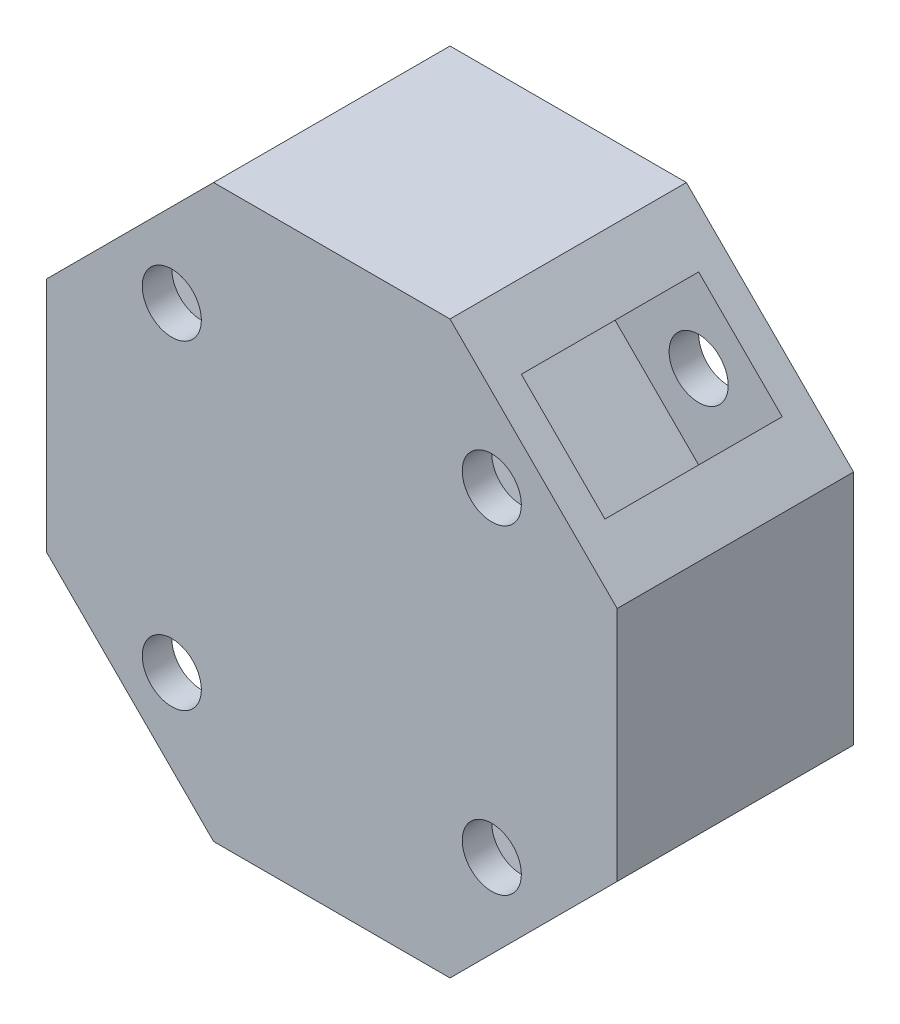
SolidWorks part; units mm, degrees
ref_plane "Front Plane" through (0, 0, 0) normal (0, 0, 1) x (1, 0, 0)
ref_plane "Top Plane" through (0, 0, 0) normal (0, 1, 0) x (1, 0, 0)
ref_plane "Right Plane" through (0, 0, 0) normal (1, 0, 0) x (0, 0, -1)
sketch "Sketch1" plane through (0, 0, 0) normal (0, 0, 1) x (1, 0, 0)
  line L0 (-30.6605, 12.7) -> (-30.6605, -12.7)
  line L1 (-12.7, -30.6605) -> (12.7, -30.6605)
  line L2 (12.7, -30.6605) -> (30.6605, -12.7)
  line L3 (30.6605, -12.7) -> (30.6605, 12.7)
  line L4 (30.6605, 12.7) -> (12.7, 30.6605)
  line L5 (12.7, 30.6605) -> (-12.7, 30.6605)
  line L6 (-12.7, 30.6605) -> (-30.6605, 12.7)
  line L7 (-30.6605, -12.7) -> (-12.7, -30.6605)
  line L8 (0, 0) -> (0, 37.9758) construction
  circle A0 centre (0, 0) radius 30.6605 construction
  dimension "D1" = 25.4
  dimension "D2" = 12.7
extrude "Boss-Extrude1" add sketch "Sketch1" along normal blind 25.4
sketch "Sketch2" plane through (21.6803, 21.6803, 0) normal (0.7071, 0.7071, 0) x (0, 0, -1)
  line L0 (-25.4, 0) -> (0, 0) construction
  line L1 (-25.4, -12.7) -> (-25.4, 12.7) construction
  line L2 (-12.7, 0) -> (-12.7, 12.7) construction
  line L3 (-25.4, 12.7) -> (0, 12.7) construction
  line L5 (-3.175, -6.35) -> (-22.225, -6.35)
  line L6 (-3.175, -6.35) -> (-3.175, 6.35)
  line L7 (-3.175, 6.35) -> (-22.225, 6.35)
  line L8 (-22.225, -6.35) -> (-22.225, 6.35)
  line L9 (-3.175, -6.35) -> (-22.225, 6.35) construction
  line L10 (-3.175, 6.35) -> (-22.225, -6.35) construction
  dimension "D1" = 19.05
  dimension "D2" = 12.7
extrude "Cut-Extrude1" cut sketch "Sketch2" against normal blind 12.7
ref_plane "Plane1" through (0, 0, 0) normal (1, 0, 0) x (0, 0, -1)
mirror "Mirror1" about plane through (0, 0, 0) normal (1, 0, 0) of "Cut-Extrude1"
ref_plane "Plane2" through (0, 0, 0) normal (0, 1, 0) x (1, 0, 0)
mirror "Mirror2" about plane through (0, 0, 0) normal (0, 1, 0) of "Mirror1"
sketch "Sketch3" plane through (0, 0, 25.4) normal (0, 0, 1) x (1, 0, 0)
  line L0 (-21.6803, 21.6803) -> (-17.1901, 17.1901) construction
  line L1 (-12.7, 30.6605) -> (-30.6605, 12.7) construction
  line L2 (0, 30.6605) -> (0, -30.6605) construction
  line L3 (12.7, 30.6605) -> (-12.7, 30.6605) construction
  line L4 (-12.7, -30.6605) -> (12.7, -30.6605) construction
  line L5 (-30.6605, 0) -> (30.6605, 0) construction
  line L6 (-30.6605, 12.7) -> (-30.6605, -12.7) construction
  line L7 (30.6605, -12.7) -> (30.6605, 12.7) construction
  circle A0 centre (-17.1901, 17.1901) radius 3.175
  circle A1 centre (-17.1901, -17.1901) radius 3.175
  circle A2 centre (17.1901, -17.1901) radius 3.175
  circle A3 centre (17.1901, 17.1901) radius 3.175
  dimension "D1" = 6.35
  dimension "D3" = 90
  dimension "D2" = 6.35
extrude "Cut-Extrude2" cut sketch "Sketch3" against normal through all
